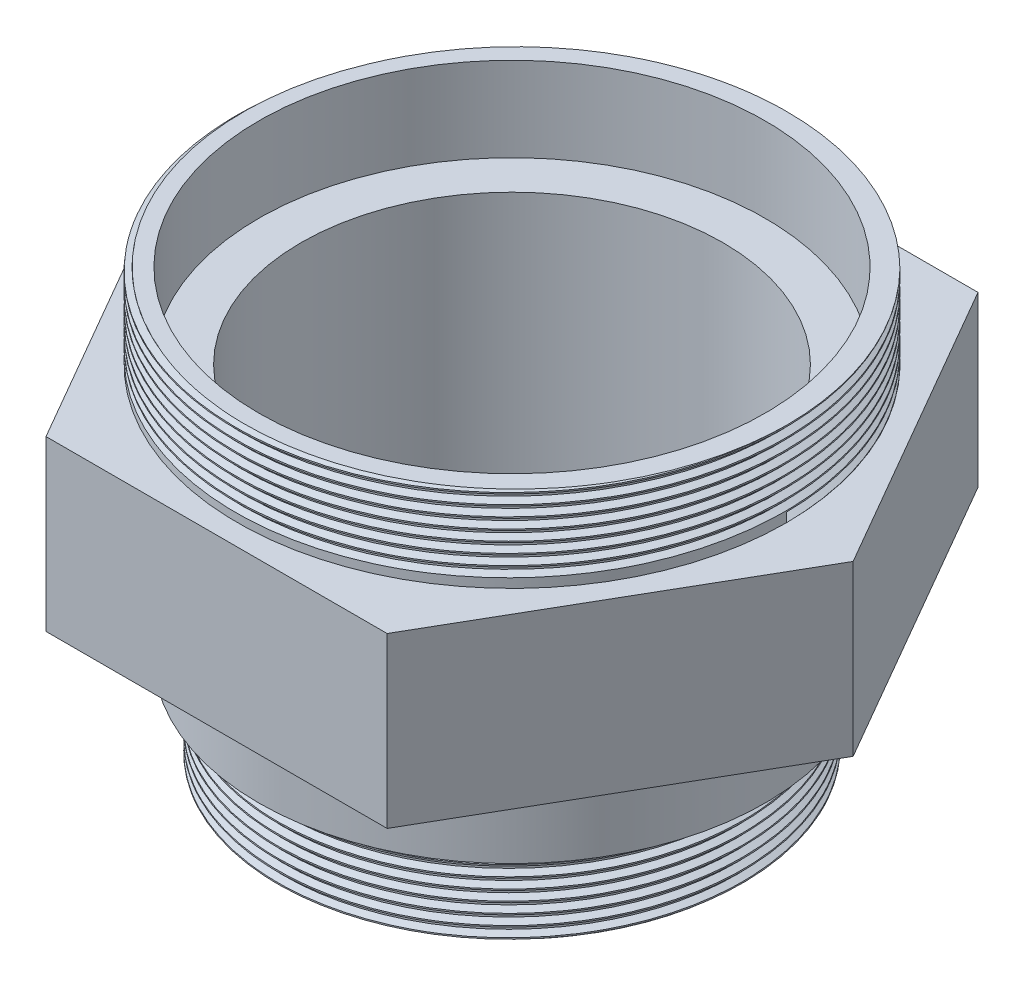
SolidWorks part; units mm, degrees
ref_plane "Front Plane" through (0, 0, 0) normal (0, 0, 1) x (1, 0, 0)
ref_plane "Top Plane" through (0, 0, 0) normal (0, 1, 0) x (1, 0, 0)
ref_plane "Right Plane" through (0, 0, 0) normal (1, 0, 0) x (0, 0, -1)
sketch "Sketch1" plane through (0, 0, 0) normal (0, 1, 0) x (1, 0, 0)
  line L1 (8.0829, 0) -> (4.0415, 7)
  line L2 (4.0415, 7) -> (-4.0415, 7)
  line L3 (-4.0415, 7) -> (-8.0829, 0)
  line L4 (-8.0829, 0) -> (-4.0415, -7)
  line L5 (-4.0415, -7) -> (4.0415, -7)
  line L6 (4.0415, -7) -> (8.0829, 0)
  circle A0 centre (0, 0) radius 5.5
  circle A1 centre (0, 0) radius 6
  circle A2 centre (0, 0) radius 7 construction
  circle A3 centre (0, 0) radius 6.5
  point P4 (0, 7)
  dimension "D1" = 11
  dimension "D2" = 12
  dimension "D3" = 14
  dimension "D4" = 13
extrude "Boss-Extrude1" add sketch "Sketch1" against normal blind 4 contours A0 region at (0, 0, 0)
extrude "Boss-Extrude2" add sketch "Sketch1<3>" against normal blind 2 contours A1
sketch "Sketch1<3>" plane through (0, 0, 0) normal (0, 1, 0) x (1, 0, 0) same geometry as "Sketch1"
extrude "Boss-Extrude3" add sketch "Sketch1<4>" along normal blind 4 contours L5 L6 L1 L2 L3 L4 A3 | A3 A1 | A1 region at (5.877, 0, 3.3931) region at (-6.3162, 0, 0)
sketch "Sketch1<4>" plane through (0, 0, 0) normal (0, 1, 0) x (1, 0, 0) same geometry as "Sketch1"
extrude "Boss-Extrude4" add sketch "Sketch1<5>" along normal blind 6 contours A3 A1 region at (-6.3162, 0, 0)
sketch "Sketch1<5>" plane through (0, 0, 0) normal (0, 1, 0) x (1, 0, 0) same geometry as "Sketch1"
thread "Thread1" pitch 0.25 method cut profile "Thread Profile1" start angle 0, offset 0, length 0, pitch 0.25, diameter 11
ref_plane "Plane1" through (-5.5, -2, 0) normal (0, 0, 1) x (-1, 0, 0)
sketch "Thread Profile1" plane through (-5.5, -2, 0) normal (0, 0, 1) x (-1, 0, 0)
  line L0 (0, 0) -> (0, 0.25) construction
  line L11 (0, 0) -> (0, 0.2187)
  line L12 (0, 0.2187) -> (-0.1353, 0.1406)
  line L13 (-0.1353, 0.1406) -> (-0.1353, 0.0781)
  line L15 (-0.1353, 0.0781) -> (0, 0)
  line L17 (-0.1353, 0.1094) -> (0, 0.1094) construction
  point P2 (0, 0)
  dimension "Pitch" = 0.25
  dimension "Profile_Angle" = 60
  dimension "Profile_Land" = 0.0625
  dimension "Profile_Height" = 0.1353
thread "Thread2" pitch 0.25 method cut profile "Thread Profile2" start angle 0, offset 0, length 0, pitch 0.25, diameter 13
ref_plane "Plane2" through (6.5, 4, 0) normal (0, 0, 1) x (1, 0, 0)
sketch "Thread Profile2" plane through (6.5, 4, 0) normal (0, 0, 1) x (1, 0, 0)
  line L0 (0, 0) -> (0, 0.25) construction
  line L11 (0, 0) -> (0, 0.2187)
  line L12 (0, 0.2187) -> (-0.1353, 0.1406)
  line L13 (-0.1353, 0.1406) -> (-0.1353, 0.0781)
  line L15 (-0.1353, 0.0781) -> (0, 0)
  line L17 (-0.1353, 0.1094) -> (0, 0.1094) construction
  point P2 (0, 0)
  dimension "Pitch" = 0.25
  dimension "Profile_Angle" = 60
  dimension "Profile_Land" = 0.0625
  dimension "Profile_Height" = 0.1353
sketch "Sketch7" plane through (0, -4, 0) normal (0, -1, 0) x (1, 0, 0)
  circle A0 centre (0, 0) radius 5
  dimension "D1" = 10
extrude "Cut-Extrude1" cut sketch "Sketch7" against normal through all both and the other way through all
other "CPoint1" parameters "Diameter"=12.7, "StubLength"=19.05
ref_axis "Axis1" through (0, 14, 0) along (0, -1, 0)
